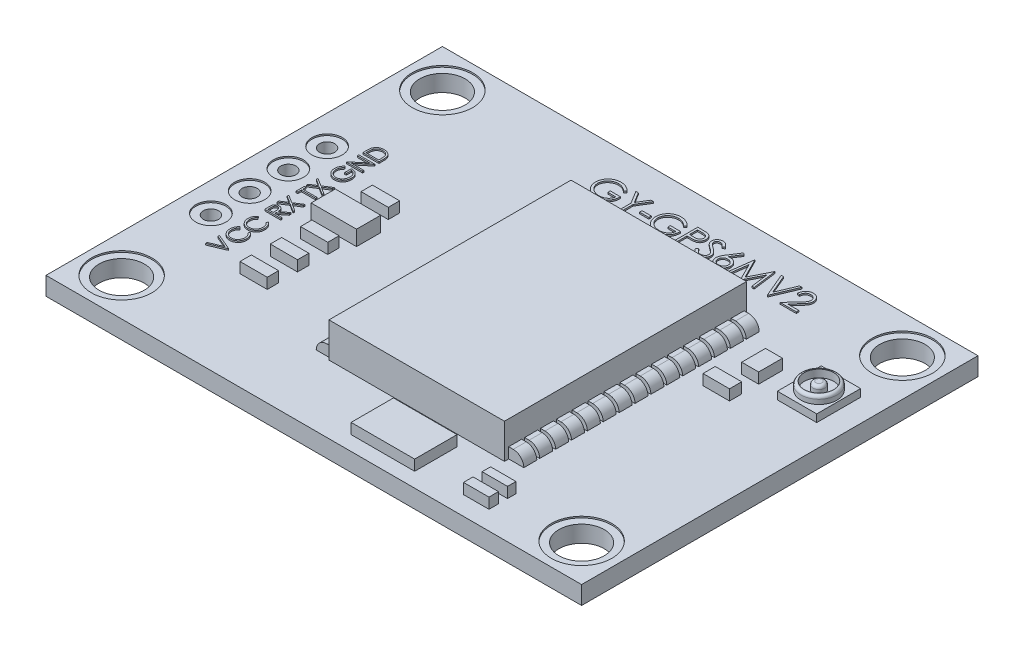
SolidWorks part; units mm, degrees
ref_plane "Front Plane" through (0, 0, 0) normal (0, 0, 1) x (1, 0, 0)
ref_plane "Top Plane" through (0, 0, 0) normal (0, 1, 0) x (1, 0, 0)
ref_plane "Right Plane" through (0, 0, 0) normal (1, 0, 0) x (0, 0, -1)
sketch "Sketch1" plane through (0, 0, 0) normal (0, 1, 0) x (1, 0, 0)
  line L1 (-38.6972, -21.6996) -> (-3.2972, -21.6996)
  line L2 (-38.6972, -21.6996) -> (-38.6972, 4.5004)
  line L3 (-38.6972, 4.5004) -> (-3.2972, 4.5004)
  line L4 (-3.2972, -21.6996) -> (-3.2972, 4.5004)
  line L5 (-38.6972, -21.6996) -> (-3.2972, 4.5004) construction
  line L6 (-38.6972, 4.5004) -> (-3.2972, -21.6996) construction
  point P0 (-20.9972, -8.5996)
  dimension "D1" = 26.2
  dimension "D2" = 35.4
extrude "Boss-Extrude1" add sketch "Sketch1" along normal blind 1.2
sketch "Sketch2" plane through (0, 1.2, 0) normal (0, 1, 0) x (1, 0, 0)
  line L0 (-3.2972, 4.5004) -> (-38.6972, 4.5004) construction
  line L1 (-38.6972, 4.5004) -> (-38.6972, -21.6996) construction
  line L2 (-3.2972, -21.6996) -> (-3.2972, 4.5004) construction
  line L3 (-38.6972, -21.6996) -> (-3.2972, -21.6996) construction
  circle A0 centre (-36.1972, 2.0004) radius 1.5
  circle A1 centre (-5.7972, 2.0004) radius 1.5
  circle A2 centre (-36.1972, -19.1996) radius 1.5
  circle A3 centre (-5.7972, -19.1996) radius 1.5
  dimension "D1" = 2.5
  dimension "D3" = 3
  dimension "D4" = 2.5
  dimension "D5" = 2.5
  dimension "D6" = 2.5
  dimension "D2" = 2.5
  dimension "D7" = 2.5
extrude "Cut-Extrude1" cut sketch "Sketch2" against normal through all
sketch "Sketch3" plane through (0, 1.2, 0) normal (0, 1, 0) x (1, 0, 0)
  line L0 (-38.6972, -21.6996) -> (-3.2972, -21.6996) construction
  line L1 (-12.8972, -17.1996) -> (-24.4972, -17.1996)
  line L2 (-12.8972, -17.1996) -> (-12.8972, -1.1996)
  line L3 (-12.8972, -1.1996) -> (-24.4972, -1.1996)
  line L4 (-24.4972, -17.1996) -> (-24.4972, -1.1996)
  line L5 (-12.8972, -17.1996) -> (-24.4972, -1.1996) construction
  line L6 (-12.8972, -1.1996) -> (-24.4972, -17.1996) construction
  line L7 (-3.2972, -21.6996) -> (-3.2972, 4.5004) construction
  point P0 (-18.6972, -9.1996)
  dimension "D1" = 16
  dimension "D2" = 11.6
  dimension "D3" = 4.5
  dimension "D4" = 9.6
extrude "Boss-Extrude2" add sketch "Sketch3" along normal blind 2.3
sketch "Sketch4" plane through (0, 1.2, 0) normal (0, 1, 0) x (1, 0, 0)
  text T0 "GY-GPS6MV2" font "Century Gothic" height in points 6
extrude "Boss-Extrude3" add sketch "Sketch4" along normal blind 0.1
sketch "Sketch5" plane through (0, 1.2, 0) normal (0, 1, 0) x (1, 0, 0)
  line L0 (-38.6972, -21.6996) -> (-3.2972, -21.6996) construction
  line L1 (-38.6972, 4.5004) -> (-38.6972, -21.6996) construction
  circle A0 centre (-36.7972, -12.6996) radius 0.5
  circle A1 centre (-36.7972, -10.1396) radius 0.5
  circle A2 centre (-36.7972, -7.5796) radius 0.5
  circle A3 centre (-36.7972, -5.0196) radius 0.5
  dimension "D3" = 1
  dimension "D1" = 9
  dimension "D2" = 1.9
  dimension "D4" = 4
extrude "Cut-Extrude2" cut sketch "Sketch5" against normal through all
sketch "Sketch6" plane through (0, 1.2, 0) normal (0, 1, 0) x (1, 0, 0)
  circle A0 centre (-36.7972, -12.6996) radius 1
  circle A1 centre (-36.7972, -10.1396) radius 1
  circle A2 centre (-36.7972, -7.5796) radius 1
  circle A3 centre (-36.7972, -5.0196) radius 1
  dimension "D1" = 4
extrude "Cut-Extrude3" cut sketch "Sketch6" against normal blind 0.1
sketch "Sketch7" plane through (0, 1.2, 0) normal (0, 1, 0) x (1, 0, 0)
  line L0 (-34.0946, -14.7456) -> (-34.0946, -2.4536) construction
  text T0 "VCC RX TX GND" font "Century Gothic" height in points 4
extrude "Boss-Extrude4" add sketch "Sketch7" along normal blind 0.1
sketch "Sketch8" plane through (0, 1.2, 0) normal (0, 1, 0) x (1, 0, 0)
  line L0 (-3.2972, 4.5004) -> (-38.6972, 4.5004) construction
  line L1 (-7.3972, -1.7596) -> (-4.7972, -1.7596)
  line L2 (-7.3972, -1.7596) -> (-7.3972, -4.6596)
  line L3 (-7.3972, -4.6596) -> (-4.7972, -4.6596)
  line L4 (-4.7972, -1.7596) -> (-4.7972, -4.6596)
  line L5 (-7.3972, -1.7596) -> (-4.7972, -4.6596) construction
  line L6 (-7.3972, -4.6596) -> (-4.7972, -1.7596) construction
  line L7 (-3.2972, -21.6996) -> (-3.2972, 4.5004) construction
  dimension "D1" = 6.26
  dimension "D2" = 1.5
  dimension "D3" = 2.9
  dimension "D4" = 2.6
extrude "Boss-Extrude5" add sketch "Sketch8" along normal blind 0.5
sketch "Sketch9" plane through (0, 1.7, 0) normal (0, 1, 0) x (1, 0, 0)
  circle A0 centre (-6.0972, -3.2096) radius 1.1879
  circle A1 centre (-6.0972, -3.2096) radius 0.972
  circle A2 centre (-6.0972, -3.2096) radius 0.3997
extrude "Boss-Extrude6" add sketch "Sketch9" along normal blind 0.5 contours A0 A1 | A2 region at (-7.2515, 1.7, 3.2096) region at (-6.0972, 1.7, 3.2096)
fillet "Fillet2" radius 0.2 1 edges at (-6.0972, 2.2, 4.3974)
fillet "Fillet3" radius 0.2 1 edges at (-6.0972, 2.2, 3.6092)
sketch "Sketch10" plane through (0, 1.2, 0) normal (0, 1, 0) x (1, 0, 0)
  line L0 (-38.6972, 4.5004) -> (-38.6972, -21.6996) construction
  line L1 (-19.4972, -17.9339) -> (-15.2972, -17.9339)
  line L2 (-19.4972, -17.9339) -> (-19.4972, -20.7339)
  line L3 (-19.4972, -20.7339) -> (-15.2972, -20.7339)
  line L4 (-15.2972, -17.9339) -> (-15.2972, -20.7339)
  dimension "D1" = 2.8
  dimension "D2" = 4.2
  dimension "D3" = 19.2
extrude "Boss-Extrude7" add sketch "Sketch10" along normal blind 0.7
sketch "Sketch11" plane through (0, 1.2, 0) normal (0, 1, 0) x (1, 0, 0)
  line L0 (-32.3787, -11.1959) -> (-30.5787, -11.1959)
  line L1 (-32.3787, -6.4459) -> (-30.5787, -6.4459)
  line L2 (-32.3787, -6.4459) -> (-32.3787, -7.1959)
  line L3 (-32.3787, -7.1959) -> (-30.5787, -7.1959)
  line L4 (-30.5787, -6.4459) -> (-30.5787, -7.1959)
  line L5 (-32.3787, -10.4459) -> (-32.3787, -11.1959)
  line L6 (-32.3787, -10.4459) -> (-30.5787, -10.4459)
  line L7 (-30.5787, -10.4459) -> (-30.5787, -11.1959)
  line L8 (-32.3787, -15.1959) -> (-30.5787, -15.1959)
  line L9 (-32.3787, -14.4459) -> (-32.3787, -15.1959)
  line L10 (-32.3787, -14.4459) -> (-30.5787, -14.4459)
  line L11 (-30.5787, -14.4459) -> (-30.5787, -15.1959)
  line L13 (-32.3787, -13.1959) -> (-30.5787, -13.1959)
  line L14 (-32.3787, -12.4459) -> (-30.5787, -12.4459)
  line L15 (-32.3787, -12.4459) -> (-32.3787, -13.1959)
  line L16 (-30.5787, -12.4459) -> (-30.5787, -13.1959)
  dimension "D1" = 1.8
  dimension "D2" = 0.75
  dimension "D3" = 3
  dimension "D4" = 2
extrude "Boss-Extrude8" add sketch "Sketch11" along normal blind 0.7
sketch "Sketch12" plane through (0, 1.2, 0) normal (0, 1, 0) x (1, 0, 0)
  line L0 (-32.3787, -7.1959) -> (-30.5787, -7.1959) construction
  line L1 (-30.0787, -9.7959) -> (-33.0787, -9.7959)
  line L2 (-30.0787, -9.7959) -> (-30.0787, -8.1959)
  line L3 (-30.0787, -8.1959) -> (-33.0787, -8.1959)
  line L4 (-33.0787, -9.7959) -> (-33.0787, -8.1959)
  line L5 (-30.5787, -7.1959) -> (-30.5787, -6.4459) construction
  dimension "D1" = 1.6
  dimension "D2" = 3
  dimension "D3" = 1
  dimension "D4" = 0.5
extrude "Boss-Extrude9" add sketch "Sketch12" along normal blind 1
sketch "Sketch13" plane through (0, 1.2, 0) normal (0, 1, 0) x (1, 0, 0)
  circle A0 centre (-36.1972, 2.0004) radius 2
  circle A1 centre (-36.1972, -19.1996) radius 2
  circle A2 centre (-5.7972, 2.0004) radius 2
  circle A3 centre (-5.7972, -19.1996) radius 2
extrude "Cut-Extrude4" cut sketch "Sketch13" against normal blind 0.1
sketch "Sketch14" plane through (0, 1.2, 0) normal (0, 1, 0) x (1, 0, 0)
  line L1 (-12.3473, -19.8234) -> (-10.6664, -19.8234)
  line L2 (-12.3473, -19.8234) -> (-12.3473, -20.4538)
  line L3 (-12.3473, -20.4538) -> (-10.6664, -20.4538)
  line L4 (-10.6664, -19.8234) -> (-10.6664, -20.4538)
  line L5 (-12.3473, -18.6678) -> (-10.6664, -18.6678)
  line L6 (-12.3473, -18.6678) -> (-12.3473, -19.2281)
  line L7 (-12.3473, -19.2281) -> (-10.6664, -19.2281)
  line L8 (-10.6664, -18.6678) -> (-10.6664, -19.2281)
  line L9 (-10.6664, -5.5003) -> (-8.9154, -5.5003)
  line L10 (-10.6664, -5.5003) -> (-10.6664, -6.3058)
  line L11 (-10.6664, -6.3058) -> (-8.9154, -6.3058)
  line L12 (-8.9154, -5.5003) -> (-8.9154, -6.3058)
  line L13 (-8.9154, -4.3797) -> (-10.036, -4.3797)
  line L14 (-8.9154, -4.3797) -> (-8.9154, -2.8038)
  line L15 (-8.9154, -2.8038) -> (-10.036, -2.8038)
  line L16 (-10.036, -4.3797) -> (-10.036, -2.8038)
extrude "Boss-Extrude10" add sketch "Sketch14" along normal blind 0.7
sketch "Sketch15" plane through (-12.8972, 0, 0) normal (1, 0, 0) x (0, 0, -1)
  line L0 (-17.1996, 1.2) -> (-1.1996, 1.2) construction
  line L1 (-16.9196, 1.9) -> (-16.0596, 1.9)
  line L2 (-16.9196, 1.9) -> (-16.9196, 1.2)
  line L3 (-16.9196, 1.2) -> (-16.0596, 1.2)
  line L4 (-16.0596, 1.9) -> (-16.0596, 1.2)
  line L5 (-15.8696, 1.9) -> (-15.8696, 1.2)
  line L6 (-15.8696, 1.9) -> (-15.0096, 1.9)
  line L7 (-15.0096, 1.9) -> (-15.0096, 1.2)
  line L8 (-15.8696, 1.2) -> (-15.0096, 1.2)
  line L9 (-14.8196, 1.9) -> (-14.8196, 1.2)
  line L10 (-14.8196, 1.9) -> (-13.9596, 1.9)
  line L11 (-13.9596, 1.9) -> (-13.9596, 1.2)
  line L12 (-14.8196, 1.2) -> (-13.9596, 1.2)
  line L13 (-13.7696, 1.9) -> (-13.7696, 1.2)
  line L14 (-13.7696, 1.9) -> (-12.9096, 1.9)
  line L15 (-12.9096, 1.9) -> (-12.9096, 1.2)
  line L16 (-13.7696, 1.2) -> (-12.9096, 1.2)
  line L17 (-12.7196, 1.9) -> (-12.7196, 1.2)
  line L18 (-12.7196, 1.9) -> (-11.8596, 1.9)
  line L19 (-11.8596, 1.9) -> (-11.8596, 1.2)
  line L20 (-12.7196, 1.2) -> (-11.8596, 1.2)
  line L21 (-11.6696, 1.9) -> (-11.6696, 1.2)
  line L22 (-11.6696, 1.9) -> (-10.8096, 1.9)
  line L23 (-10.8096, 1.9) -> (-10.8096, 1.2)
  line L24 (-11.6696, 1.2) -> (-10.8096, 1.2)
  line L25 (-10.6196, 1.9) -> (-10.6196, 1.2)
  line L26 (-10.6196, 1.9) -> (-9.7596, 1.9)
  line L27 (-9.7596, 1.9) -> (-9.7596, 1.2)
  line L28 (-10.6196, 1.2) -> (-9.7596, 1.2)
  line L29 (-9.5696, 1.9) -> (-9.5696, 1.2)
  line L30 (-9.5696, 1.9) -> (-8.7096, 1.9)
  line L31 (-8.7096, 1.9) -> (-8.7096, 1.2)
  line L32 (-9.5696, 1.2) -> (-8.7096, 1.2)
  line L33 (-8.5196, 1.9) -> (-8.5196, 1.2)
  line L34 (-8.5196, 1.9) -> (-7.6596, 1.9)
  line L35 (-7.6596, 1.9) -> (-7.6596, 1.2)
  line L36 (-8.5196, 1.2) -> (-7.6596, 1.2)
  line L37 (-7.4696, 1.9) -> (-7.4696, 1.2)
  line L38 (-7.4696, 1.9) -> (-6.6096, 1.9)
  line L39 (-6.6096, 1.9) -> (-6.6096, 1.2)
  line L40 (-7.4696, 1.2) -> (-6.6096, 1.2)
  line L41 (-6.4196, 1.9) -> (-6.4196, 1.2)
  line L42 (-6.4196, 1.9) -> (-5.5596, 1.9)
  line L43 (-5.5596, 1.9) -> (-5.5596, 1.2)
  line L44 (-6.4196, 1.2) -> (-5.5596, 1.2)
  line L45 (-5.3696, 1.9) -> (-5.3696, 1.2)
  line L46 (-5.3696, 1.9) -> (-4.5096, 1.9)
  line L47 (-4.5096, 1.9) -> (-4.5096, 1.2)
  line L48 (-5.3696, 1.2) -> (-4.5096, 1.2)
  line L49 (-4.3196, 1.9) -> (-4.3196, 1.2)
  line L50 (-4.3196, 1.9) -> (-3.4596, 1.9)
  line L51 (-3.4596, 1.9) -> (-3.4596, 1.2)
  line L52 (-4.3196, 1.2) -> (-3.4596, 1.2)
  line L53 (-3.2696, 1.9) -> (-3.2696, 1.2)
  line L54 (-3.2696, 1.9) -> (-2.4096, 1.9)
  line L55 (-2.4096, 1.9) -> (-2.4096, 1.2)
  line L56 (-3.2696, 1.2) -> (-2.4096, 1.2)
  line L57 (-2.2196, 1.9) -> (-2.2196, 1.2)
  line L58 (-2.2196, 1.9) -> (-1.3596, 1.9)
  line L59 (-1.3596, 1.9) -> (-1.3596, 1.2)
  line L60 (-2.2196, 1.2) -> (-1.3596, 1.2)
  line L62 (-17.1996, 3.5) -> (-17.1996, 1.2) construction
  dimension "D2" = 0.7
  dimension "D3" = 0.86
  dimension "D4" = 0.28
  dimension "D1" = 15
extrude "Boss-Extrude11" add sketch "Sketch15" along normal blind 1
fillet "Fillet5" radius 0.7 15 edges at (-11.8972, 1.9, 1.7896) (-11.8972, 1.9, 2.8396) (-11.8972, 1.9, 3.8896) (-11.8972, 1.9, 4.9396) (-11.8972, 1.9, 5.9896) (-11.8972, 1.9, 7.0396) (-11.8972, 1.9, 9.1396) (-11.8972, 1.9, 8.0896) (-11.8972, 1.9, 10.1896) (-11.8972, 1.9, 11.2396) (-11.8972, 1.9, 12.2896) (-11.8972, 1.9, 13.3396) (-11.8972, 1.9, 14.3896) (-11.8972, 1.9, 15.4396) (-11.8972, 1.9, 16.4896)
sketch "Sketch16" plane through (-24.4972, 0, 0) normal (-1, 0, 0) x (0, 0, 1)
  line L0 (-4.5004, 1.2) -> (21.6996, 1.2) construction
  line L1 (1.4796, 1.9) -> (2.3396, 1.9)
  line L2 (1.4796, 1.9) -> (1.4796, 1.2)
  line L3 (1.4796, 1.2) -> (2.3396, 1.2)
  line L4 (2.3396, 1.9) -> (2.3396, 1.2)
  line L5 (1.1996, 3.5) -> (1.1996, 1.2) construction
  line L6 (2.5296, 1.9) -> (3.3896, 1.9)
  line L7 (2.5296, 1.9) -> (2.5296, 1.2)
  line L8 (2.5296, 1.2) -> (3.3896, 1.2)
  line L9 (3.3896, 1.9) -> (3.3896, 1.2)
  line L10 (3.5796, 1.9) -> (4.4396, 1.9)
  line L11 (3.5796, 1.9) -> (3.5796, 1.2)
  line L12 (3.5796, 1.2) -> (4.4396, 1.2)
  line L13 (4.4396, 1.9) -> (4.4396, 1.2)
  line L14 (4.6296, 1.9) -> (5.4896, 1.9)
  line L15 (4.6296, 1.9) -> (4.6296, 1.2)
  line L16 (4.6296, 1.2) -> (5.4896, 1.2)
  line L17 (5.4896, 1.9) -> (5.4896, 1.2)
  line L18 (5.6796, 1.9) -> (6.5396, 1.9)
  line L19 (5.6796, 1.9) -> (5.6796, 1.2)
  line L20 (5.6796, 1.2) -> (6.5396, 1.2)
  line L21 (6.5396, 1.9) -> (6.5396, 1.2)
  line L22 (6.7296, 1.9) -> (7.5896, 1.9)
  line L23 (6.7296, 1.9) -> (6.7296, 1.2)
  line L24 (6.7296, 1.2) -> (7.5896, 1.2)
  line L25 (7.5896, 1.9) -> (7.5896, 1.2)
  line L26 (7.7796, 1.9) -> (8.6396, 1.9)
  line L27 (7.7796, 1.9) -> (7.7796, 1.2)
  line L28 (7.7796, 1.2) -> (8.6396, 1.2)
  line L29 (8.6396, 1.9) -> (8.6396, 1.2)
  line L30 (8.8296, 1.9) -> (9.6896, 1.9)
  line L31 (8.8296, 1.9) -> (8.8296, 1.2)
  line L32 (8.8296, 1.2) -> (9.6896, 1.2)
  line L33 (9.6896, 1.9) -> (9.6896, 1.2)
  line L34 (9.8796, 1.9) -> (10.7396, 1.9)
  line L35 (9.8796, 1.9) -> (9.8796, 1.2)
  line L36 (9.8796, 1.2) -> (10.7396, 1.2)
  line L37 (10.7396, 1.9) -> (10.7396, 1.2)
  line L38 (10.9296, 1.9) -> (11.7896, 1.9)
  line L39 (10.9296, 1.9) -> (10.9296, 1.2)
  line L40 (10.9296, 1.2) -> (11.7896, 1.2)
  line L41 (11.7896, 1.9) -> (11.7896, 1.2)
  line L42 (11.9796, 1.9) -> (12.8396, 1.9)
  line L43 (11.9796, 1.9) -> (11.9796, 1.2)
  line L44 (11.9796, 1.2) -> (12.8396, 1.2)
  line L45 (12.8396, 1.9) -> (12.8396, 1.2)
  line L46 (13.0296, 1.9) -> (13.8896, 1.9)
  line L47 (13.0296, 1.9) -> (13.0296, 1.2)
  line L48 (13.0296, 1.2) -> (13.8896, 1.2)
  line L49 (13.8896, 1.9) -> (13.8896, 1.2)
  line L50 (14.0796, 1.9) -> (14.9396, 1.9)
  line L51 (14.0796, 1.9) -> (14.0796, 1.2)
  line L52 (14.0796, 1.2) -> (14.9396, 1.2)
  line L53 (14.9396, 1.9) -> (14.9396, 1.2)
  line L54 (15.1296, 1.9) -> (15.9896, 1.9)
  line L55 (15.1296, 1.9) -> (15.1296, 1.2)
  line L56 (15.1296, 1.2) -> (15.9896, 1.2)
  line L57 (15.9896, 1.9) -> (15.9896, 1.2)
  line L58 (16.1796, 1.9) -> (17.0396, 1.9)
  line L59 (16.1796, 1.9) -> (16.1796, 1.2)
  line L60 (16.1796, 1.2) -> (17.0396, 1.2)
  line L61 (17.0396, 1.9) -> (17.0396, 1.2)
  dimension "D1" = 0.28
  dimension "D2" = 0.86
  dimension "D3" = 0.7
  dimension "D4" = 15
extrude "Boss-Extrude12" add sketch "Sketch16" along normal blind 1
fillet "Fillet6" radius 0.7 15 edges at (-25.4972, 1.9, 16.6096) (-25.4972, 1.9, 15.5596) (-25.4972, 1.9, 14.5096) (-25.4972, 1.9, 13.4596) (-25.4972, 1.9, 12.4096) (-25.4972, 1.9, 11.3596) (-25.4972, 1.9, 10.3096) (-25.4972, 1.9, 9.2596) (-25.4972, 1.9, 8.2096) (-25.4972, 1.9, 7.1596) (-25.4972, 1.9, 6.1096) (-25.4972, 1.9, 5.0596) (-25.4972, 1.9, 4.0096) (-25.4972, 1.9, 2.9596) (-25.4972, 1.9, 1.9096)
